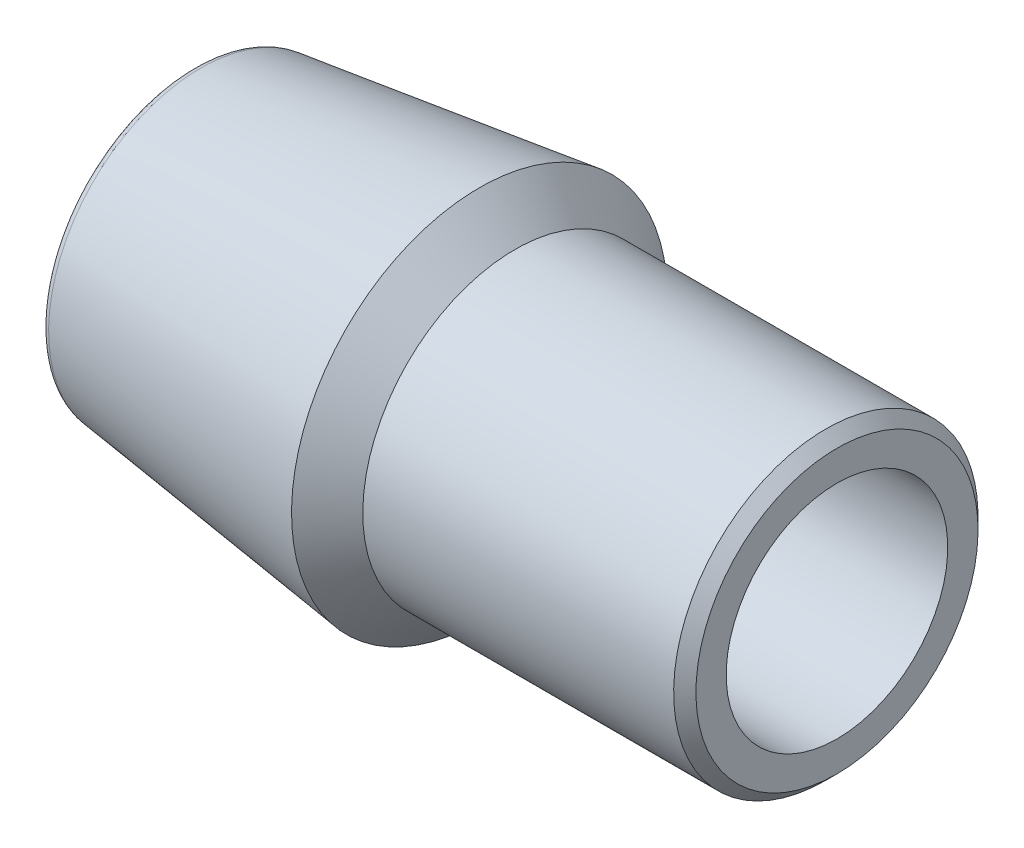
SolidWorks part; units mm, degrees
ref_plane "Front Plane" through (0, 0, 0) normal (0, 0, 1) x (1, 0, 0)
ref_plane "Top Plane" through (0, 0, 0) normal (0, 1, 0) x (1, 0, 0)
ref_plane "Right Plane" through (0, 0, 0) normal (1, 0, 0) x (0, 0, -1)
sketch "Sketch1" plane through (0, 0, 0) normal (0, 0, 1) x (1, 0, 0)
  line L0 (-19.05, 0) -> (19.05, 0) construction
  line L1 (-19.05, -4.7625) -> (-19.05, 4.7625) construction
  line L2 (-2.1082, -11.1125) -> (-2.1082, 11.1125) construction
  line L3 (-20.0422, 4.8771) -> (-18.9839, 4.8771) construction
  line L4 (-18.9839, 4.8771) -> (-19.513, 3.9605) construction
  line L5 (-19.513, 3.9605) -> (-20.0422, 4.8771) construction
  line L6 (-19.513, 4.8771) -> (-19.513, 4.7625) construction
  line L7 (-19.513, 4.7625) -> (-19.513, 4.0751) construction
  line L8 (-19.513, 4.0751) -> (-19.513, 3.9605) construction
  line L9 (-20.0091, 4.8198) -> (-19.0169, 4.8198) construction
  line L10 (-19.5792, 4.0751) -> (-19.4469, 4.0751) construction
  line L11 (-19.976, 4.7625) -> (-19.05, 4.7625) construction
  line L12 (19.05, -9.0043) -> (19.05, 9.0043)
  line L13 (-2.1082, 11.1125) -> (0, 9.0043) construction
  point P3 (-2.1082, 0)
  point P4 (0, 0)
  point P8 (-19.05, 0)
  point P11 (4.7752, 0)
  point P20 (-19.513, 4.8198)
  point P23 (-19.513, 4.0751)
  point P26 (-19.513, 4.7625)
  point P28 (19.05, 0)
  dimension "Thread Size" = 9.525
  dimension "Thread Pitch" = 1.0583
  dimension "D1" = 0.1323
  dimension "For Tube OD" = 22.225
  dimension "Height" = 38.1
  dimension "For Tube Wall Thickness" = 2.1082
  dimension "Top Height" = 19.05
  dimension "D3" = 45
  dimension "Thread Length" = 23.8252
sketch "Sketch2" plane through (0, 0, 0) normal (0, 0, 1) x (1, 0, 0)
  line L0 (-19.05, 0) -> (19.05, 0) construction
  line L1 (-19.05, 0) -> (19.05, 0) construction
  line L2 (-19.05, 4.7625) -> (-19.05, 8.4815)
  line L4 (-2.1082, 11.1125) -> (0, 9.0043)
  line L5 (0, 9.0043) -> (18.3912, 9.0043)
  line L6 (19.05, 8.3455) -> (19.05, 4.7625) construction
  line L7 (4.7752, 4.7625) -> (-19.05, 4.7625)
  line L11 (-18.5898, 9.0043) -> (-2.1082, 11.1125)
  line L14 (18.3912, 9.0043) -> (19.05, 8.3455)
  line L15 (4.7752, 4.7625) -> (4.7752, 6.2246)
  line L16 (5.1046, 6.554) -> (19.05, 6.554)
  line L17 (19.05, 6.554) -> (19.05, 8.3455)
  arc A0 (-19.05, 8.4815) -> (-18.5898, 9.0043) centre (-18.523, 8.4815) cw
  arc A1 (4.7752, 6.2246) -> (5.1046, 6.554) centre (5.1046, 6.2246) cw
  point P22 (-19.05, 8.9454)
  dimension "D9" = 0.5271
  dimension "D12" = 0.3294
  dimension "D1" = 45
  dimension "D11" = 45
  dimension "D10" = 0.6588
revolve "Revolve1" add sketch "Sketch2" angle 360 about L1
sketch "Sketch3" plane through (0, 0, 0) normal (0, 0, 1) x (1, 0, 0)
  line L0 (4.7752, 4.7625) -> (4.7752, 6.2246)
  line L3 (4.7752, 4.7625) -> (-19.05, 4.7625)
  line L5 (4.7752, -6.2246) -> (4.7752, 6.2246) construction
  line L6 (5.1046, -6.554) -> (19.05, -6.554) construction
  line L7 (19.05, 6.554) -> (5.1046, 6.554) construction
  line L8 (19.05, 6.554) -> (5.1046, 6.554)
  line L9 (-19.05, -4.7625) -> (4.7752, -4.7625) construction
  line L10 (5.1046, -6.554) -> (19.05, -6.554)
  line L11 (4.7752, -6.2246) -> (4.7752, -4.7625)
  line L12 (-19.05, -4.7625) -> (4.7752, -4.7625)
  arc A0 (5.1046, 6.554) -> (4.7752, 6.2246) centre (5.1046, 6.2246) ccw construction
  arc A1 (5.1046, 6.554) -> (4.7752, 6.2246) centre (5.1046, 6.2246) ccw
  arc A2 (4.7752, -6.2246) -> (5.1046, -6.554) centre (5.1046, -6.2246) ccw construction
  arc A3 (4.7752, -6.2246) -> (5.1046, -6.554) centre (5.1046, -6.2246) ccw
sketch "Sketch7" plane through (-19.05, 0, 0) normal (-1, 0, 0) x (0, 0, 1)
  line L0 (0, 0) -> (-2.8815, -2.8815)
  line L1 (0, -9.0043) -> (0, 9.0043) construction
  circle A0 centre (0, 0) radius 4.0751 construction
  circle A1 centre (0, 0) radius 11.1125 construction
  circle A2 centre (0, 0) radius 11.1125
  dimension "D1" = 45
sketch "Sketch4" plane through (-19.05, 0, 0) normal (-1, 0, 0) x (0, 0, 1)
  circle A0 centre (0, 0) radius 4.7625
curve "Helix/Spiral1" pitch 1.0583 height 24.8835 radius 4.7625 centre (-19.05, 0, 0) axis (1, 0, 0) start towards (0, 1, 0)
sketch "Sketch5" plane through (0, 0, 0) normal (0, 0, 1) x (1, 0, 0)
  line L0 (-20.0091, 4.8198) -> (-19.0169, 4.8198)
  line L1 (-19.0169, 4.8198) -> (-19.4469, 4.0751)
  line L2 (-19.4469, 4.0751) -> (-19.5792, 4.0751)
  line L3 (-19.5792, 4.0751) -> (-20.0091, 4.8198)
  line L4 (-19.513, 3.9605) -> (-20.0422, 4.8771) construction
sweep "Sweep1" add profiles "Sketch5" path "Helix/Spiral1"
sketch "Sketch6" plane through (0, 0, 0) normal (0, 0, 1) x (1, 0, 0)
  line L0 (-20.0422, 4.8771) -> (-19.05, 4.8771)
  line L1 (-19.05, 8.4815) -> (-19.05, -8.4815) construction
  line L2 (-19.05, 4.8771) -> (-19.05, 4.7625)
  line L3 (-19.05, -4.7625) -> (-19.05, 4.7625) construction
  line L4 (-19.05, 4.7625) -> (-18.248, 3.9605)
  line L5 (-18.248, 3.9605) -> (-20.0422, 3.9605)
  line L6 (-20.0422, 3.9605) -> (-20.0422, 4.8771)
  line L7 (4.7752, 4.8198) -> (3.9159, 3.9605)
  line L9 (3.9159, 3.9605) -> (19.05, 3.9605)
  line L10 (19.05, 3.9605) -> (19.05, 4.8198)
  line L11 (19.05, 4.8198) -> (4.7752, 4.8198)
  line L12 (-19.05, 0) -> (19.05, 0) construction
  line L13 (-19.05, 0) -> (19.05, 0) construction
  line L16 (19.05, -9.0043) -> (19.05, 9.0043) construction
  line L17 (-20.0091, 4.8198) -> (-19.0169, 4.8198) construction
  dimension "D1" = 45
  dimension "D2" = 45
revolve "Cut-Revolve1" cut sketch "Sketch6" angle 360 about L13
equation "\"D1@Sketch1\"=\"Thread Pitch@Sketch1\"/8"
equation "\"D9@Sketch2\"=\"For Tube Wall Thickness@Sketch1\" * 0.25"
equation "\"D4@Helix/Spiral1\"=\"Thread Pitch@Sketch1\""
equation "\"D3@Helix/Spiral1\"=\"Thread Length@Sketch1\"+\"Thread Pitch@Sketch1\""
equation "\"D12@Sketch2\"=\"D10@Sketch2\"*0.5"
equation "\"D10@Sketch2\"=if(\"For Tube Wall Thickness@Sketch1\">0.1,\"For Tube Wall Thickness@Sketch1\" * 0.125, \"For Tube Wall Thickness@Sketch1\" * 0.3125)"
